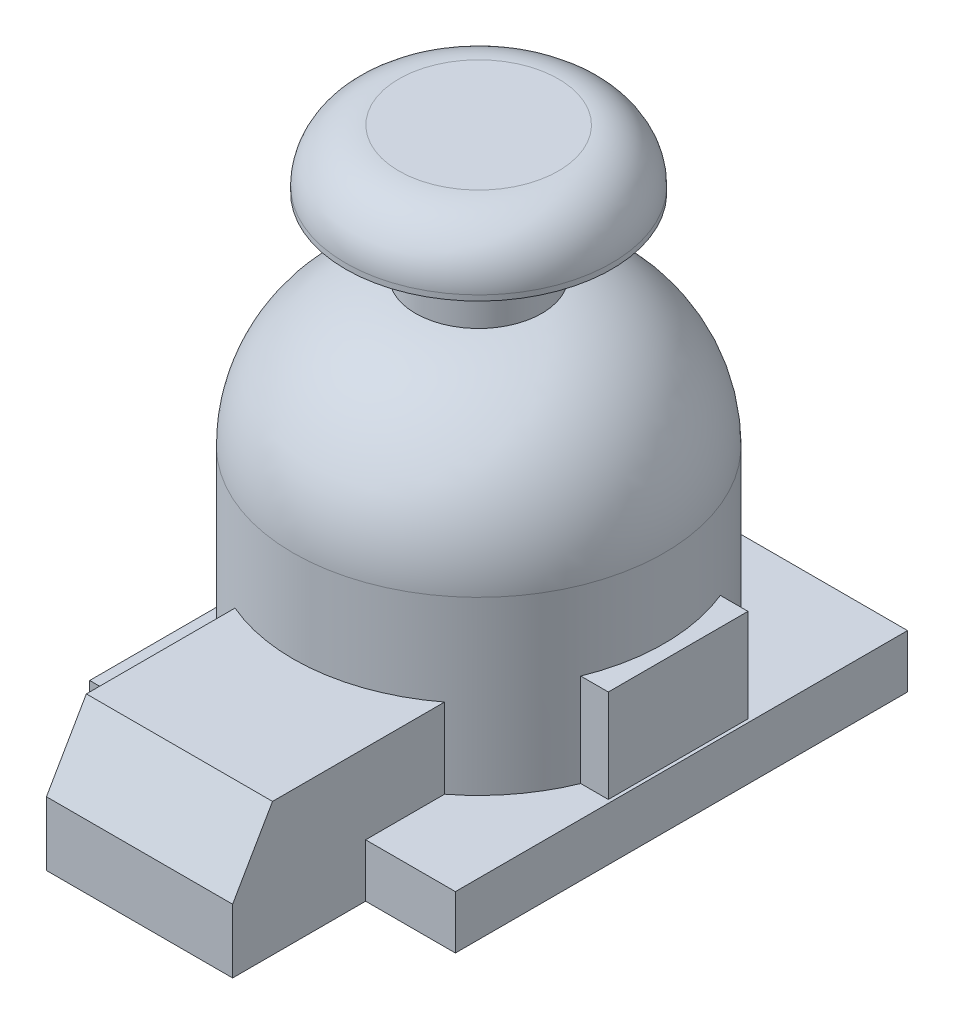
SolidWorks part; units mm, degrees
ref_plane "Спереди" through (0, 0, 0) normal (0, 0, 1) x (1, 0, 0)
ref_plane "Сверху" through (0, 0, 0) normal (0, 1, 0) x (1, 0, 0)
ref_plane "Справа" through (0, 0, 0) normal (1, 0, 0) x (0, 0, -1)
sketch "Sketch1" plane through (0, 0, 0) normal (0, 1, 0) x (1, 0, 0)
  line L1 (13.75, -17) -> (-13.75, -17)
  line L2 (13.75, -17) -> (13.75, 17)
  line L3 (13.75, 17) -> (-13.75, 17)
  line L4 (-13.75, -17) -> (-13.75, 17)
  line L5 (13.75, -17) -> (-13.75, 17) construction
  line L6 (13.75, 17) -> (-13.75, -17) construction
  point P0 (0, 0)
  dimension "D1" = 27.5
  dimension "D2" = 34
extrude "Boss-Extrude1" add sketch "Sketch1" along normal blind 4
sketch "Sketch2" plane through (0, 4, 0) normal (0, 1, 0) x (1, 0, 0)
  line L0 (13.75, 0) -> (-13.75, 0) construction
  line L1 (7, -8.5) -> (-10, -8.5)
  line L2 (7, -8.5) -> (7, 8.5)
  line L3 (7, 8.5) -> (-10, 8.5)
  line L4 (-10, -8.5) -> (-10, 8.5)
  line L5 (7, -8.5) -> (-10, 8.5) construction
  line L6 (7, 8.5) -> (-10, -8.5) construction
  line L7 (13.75, -17) -> (13.75, 17) construction
  line L8 (-13.75, 17) -> (-13.75, -17) construction
  point P0 (-1.5, 0)
  dimension "D1" = 17
  dimension "D2" = 1.5
extrude "Boss-Extrude2" add sketch "Sketch2" along normal blind 12.9
sketch "Sketch3" plane through (0, 16.9, 0) normal (0, 1, 0) x (1, 0, 0)
  circle A0 centre (0, 0) radius 1.9
  dimension "D1" = 3.8
extrude "Boss-Extrude3" add sketch "Sketch3" along normal blind 6.9
sketch "Sketch4" plane through (-10, 0, 0) normal (-1, 0, 0) x (0, 0, 1)
  line L0 (0, 16.9) -> (0, 4) construction
  line L1 (-8.5, 16.9) -> (8.5, 16.9) construction
  line L2 (-8.5, 4) -> (8.5, 4) construction
  line L4 (5.2, 4) -> (-5.2, 4)
  line L5 (5.2, 4) -> (5.2, 16.9)
  line L6 (5.2, 16.9) -> (-5.2, 16.9)
  line L7 (-5.2, 4) -> (-5.2, 16.9)
  line L8 (5.2, 4) -> (-5.2, 16.9) construction
  line L9 (5.2, 16.9) -> (-5.2, 4) construction
  point P6 (0, 10.45)
  dimension "D1" = 10.4
extrude "Boss-Extrude4" add sketch "Sketch4" along normal up to vertex (3.75 mm away) up to point (-13.75, 4, 17)
sketch "Sketch5" plane through (0, 0, -8.5) normal (0, 0, -1) x (-1, 0, 0)
  line L0 (1.5, 16.9) -> (1.5, 4) construction
  line L1 (-7, 16.9) -> (10, 16.9) construction
  line L2 (-7, 4) -> (10, 4) construction
  line L4 (-4, 4) -> (7, 4)
  line L5 (-4, 4) -> (-4, 16.9)
  line L6 (-4, 16.9) -> (7, 16.9)
  line L7 (7, 4) -> (7, 16.9)
  line L8 (-4, 4) -> (7, 16.9) construction
  line L9 (-4, 16.9) -> (7, 4) construction
  point P6 (1.5, 10.45)
  dimension "D1" = 11
extrude "Boss-Extrude5" add sketch "Sketch5" along normal blind 5
sketch "Sketch6" plane through (7, 0, 0) normal (1, 0, 0) x (0, 0, -1)
  line L0 (0, 16.9) -> (0, 4) construction
  line L1 (-8.5, 16.9) -> (8.5, 16.9) construction
  line L2 (-8.5, 4) -> (8.5, 4) construction
  line L4 (-5.25, 11) -> (5.25, 11)
  line L5 (-5.25, 11) -> (-5.25, 4)
  line L6 (-5.25, 4) -> (5.25, 4)
  line L7 (5.25, 11) -> (5.25, 4)
  line L8 (-5.25, 11) -> (5.25, 4) construction
  line L9 (-5.25, 4) -> (5.25, 11) construction
  point P6 (0, 7.5)
  dimension "D1" = 10.5
  dimension "D2" = 7
extrude "Boss-Extrude6" add sketch "Sketch6" along normal blind 6.5
sketch "Sketch8" plane through (0, 16.9, 0) normal (0, 1, 0) x (1, 0, 0)
  line L0 (7, 8.5) -> (-10, -8.5) construction
  circle A0 centre (-1.5, 0) radius 13.95
  point P8 (-1.5, 0)
  dimension "D1" = 27.9
extrude "Boss-Extrude7" add sketch "Sketch8" along normal blind 11 and the other way up to surface (12.9 mm away) other way up to face at (-0.925, 4, -2.2)
fillet "Fillet1" radius 11 1 edges at (-1.5, 27.9, 13.95)
sketch "Sketch9" plane through (0, 27.9, 0) normal (0, 1, 0) x (1, 0, 0)
  circle A0 centre (-1.5, 0) radius 4.75
extrude "Boss-Extrude8" add sketch "Sketch9" along normal blind 5.5
sketch "Sketch10" plane through (0, 33.4, 0) normal (0, 1, 0) x (1, 0, 0)
  circle A0 centre (-1.5, 0) radius 10
  dimension "D1" = 20
extrude "Boss-Extrude9" add sketch "Sketch10" along normal blind 4.4
fillet "Fillet2" radius 4 1 edges at (-1.5, 37.8, 10)
sketch "Sketch11" plane through (0, 4, 0) normal (0, 1, 0) x (1, 0, 0)
  line L0 (-13.75, -15) -> (13.75, -15) construction
  line L1 (-13.75, 17) -> (-13.75, 6.6738) construction
  line L2 (13.75, -17) -> (13.75, 17) construction
  line L3 (-13.75, -17) -> (13.75, -17) construction
  line L4 (7, -13) -> (7, -7.33)
  line L5 (7, -17) -> (-7, -17)
  line L6 (7, -17) -> (7, -13)
  line L7 (7, -7.33) -> (-7, -7.33)
  line L8 (-7, -17) -> (-7, -13)
  line L9 (7, -17) -> (-7, -13) construction
  line L10 (7, -13) -> (-7, -17) construction
  line L11 (-7, -7.33) -> (-7, -13)
  point P8 (0, -15)
  dimension "D1" = 2
  dimension "D3" = 14
extrude "Boss-Extrude10" add sketch "Sketch11" along normal blind 6
sketch "Sketch12" plane through (0, 0, 17) normal (0, 0, 1) x (1, 0, 0)
  line L0 (-7, 9) -> (7, 9) construction
  line L1 (-7, 10) -> (-7, 4) construction
  line L2 (7, 10) -> (7, 4) construction
  circle A0 centre (-5.5, 9) radius 1
  circle A1 centre (-2.5, 9) radius 1
  circle A2 centre (0.5, 9) radius 1
  circle A3 centre (3.5, 9) radius 1
  dimension "D1" = 1
  dimension "D2" = 3
  dimension "D3" = 3
  dimension "D4" = 3
  dimension "D5" = 1.5
extrude "Boss-Extrude11" add sketch "Sketch12" along normal blind 5.7
fillet "Fillet4" radius 0.5 4 edges at (4.5, 9, 17) (1.5, 9, 17) (-1.5, 9, 17) (-4.5, 9, 17)
sketch "Sketch15" plane through (0, 0, 17) normal (0, 0, 1) x (1, 0, 0)
  line L0 (-7, 10) -> (-7, 0)
  line L1 (-13.75, 0) -> (13.75, 0) construction
  line L2 (-7, 0) -> (7, 0)
  line L3 (7, 0) -> (7, 10)
  line L4 (7, 10) -> (-7, 10)
extrude "Boss-Extrude12" add sketch "Sketch15" along normal blind 10
chamfer "Chamfer1" distance 2 angle 45 1 edges at (-13.75, 2, -17)
chamfer "Chamfer2" distance 3 angle 60 1 edges at (0, 10, 27) first distance on face at (0.0597, 10, 19.9455)
